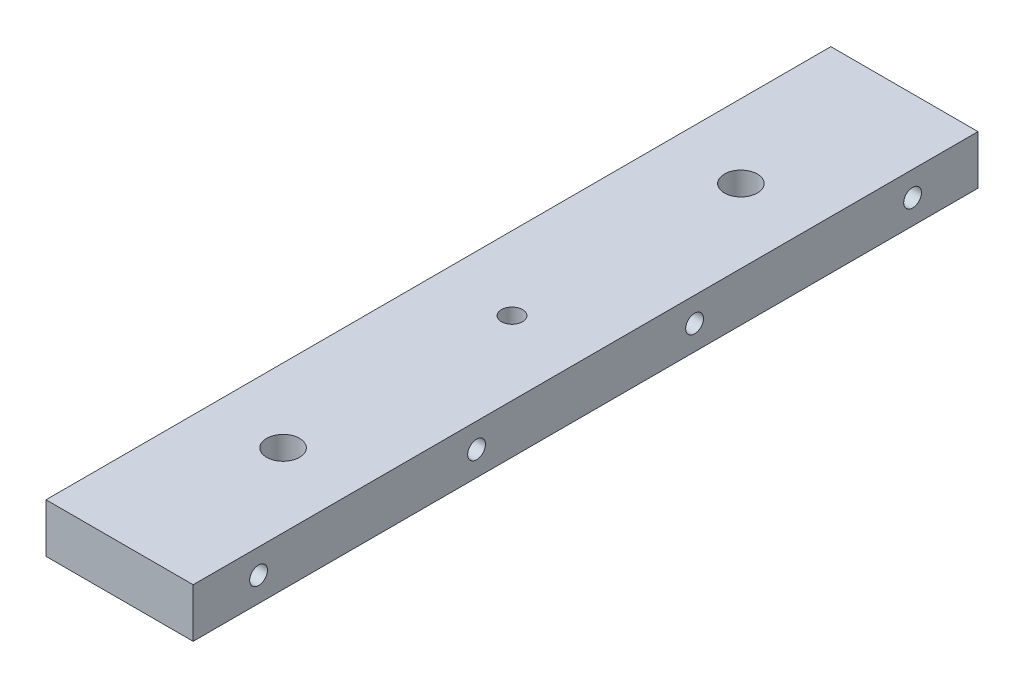
SolidWorks part; units mm, degrees
ref_plane "Front Plane" through (0, 0, 0) normal (0, 0, 1) x (1, 0, 0)
ref_plane "Top Plane" through (0, 0, 0) normal (0, 1, 0) x (1, 0, 0)
ref_plane "Right Plane" through (0, 0, 0) normal (1, 0, 0) x (0, 0, -1)
sketch "Sketch2" plane through (0, 0, 0) normal (0, 1, 0) x (1, 0, 0)
  line L0 (0, 0) -> (0, 152.4)
  line L1 (0, 152.4) -> (28.575, 152.4)
  line L2 (28.575, 152.4) -> (28.575, 0)
  line L3 (28.575, 0) -> (0, 0)
  dimension "D1" = 152.4
  dimension "D2" = 28.575
extrude "Boss-Extrude1" add sketch "Sketch2" along normal blind 9.525
sketch "Sketch3" plane through (0, 0, 0) normal (-1, 0, 0) x (0, 0, 1)
  line L3 (-152.4, 9.525) -> (0, 9.525) construction
  line L4 (-152.4, 9.525) -> (-152.4, 0) construction
  point P6 (-139.7, 4.7625)
  point P14 (-139.7, 4.7625)
  dimension "D1" = 4.7625
  dimension "D2" = 12.7
sketch "Sketch8" plane through (0, 0, 0) normal (-1, 0, 0) x (0, 0, 1)
  point P0 (-139.7, 4.7625)
hole_wizard "#5 Clearance Hole3" positions "Sketch8" profile "Sketch9" hole size "#5" standard "ANSI Inch"
sketch "Sketch9" plane through (0, 4.7625, -139.7) normal (0, 1, 0) x (0, 0, 1)
  line L0 (0, 0) -> (0, 13.7378)
  line L1 (0, 13.7378) -> (1.7272, 12.7)
  line L2 (1.7272, 12.7) -> (1.7272, 0)
  line L5 (1.7272, 0) -> (0, 0)
  line L10 (0, 13.7378) -> (-1.7272, 12.7) construction
  line L11 (0, -6.35) -> (0, 107.95) construction
  dimension "Hole Dia." = 3.4544
  dimension "Hole Depth" = 12.7
  dimension "Drill Angle" = 118
pattern_linear "LPattern1" count 4 spacing 42.3333 along (0, 0, 1) of "#5 Clearance Hole3"
sketch "Sketch10" plane through (28.575, 0, 0) normal (1, 0, 0) x (0, 0, -1)
  line L0 (0, 9.525) -> (0, 0) construction
  line L1 (0, 9.525) -> (152.4, 9.525) construction
  point P0 (12.7, 4.7625)
  point P1 (12.7, 4.7625)
  point P5 (0, 4.7625)
  point P9 (12.7, 4.7625)
  dimension "D1" = 12.7
  dimension "D2" = 4.7625
hole_wizard "#5 Clearance Hole4" positions "Sketch10" profile "Sketch11" hole size "#5" standard "ANSI Inch"
sketch "Sketch11" plane through (28.575, 4.7625, -12.7) normal (0, 1, 0) x (0, 0, -1)
  line L0 (0, 0) -> (0, 13.7378)
  line L1 (0, 13.7378) -> (1.7272, 12.7)
  line L2 (1.7272, 12.7) -> (1.7272, 0)
  line L5 (1.7272, 0) -> (0, 0)
  line L10 (0, 13.7378) -> (-1.7272, 12.7) construction
  line L11 (0, -6.35) -> (0, 107.95) construction
  dimension "Hole Dia." = 3.4544
  dimension "Hole Depth" = 12.7
  dimension "Drill Angle" = 118
pattern_linear "LPattern2" count 4 spacing 42.3333 along (0, 0, -1) of "#5 Clearance Hole4"
sketch "Sketch12" plane through (0, 9.525, 0) normal (0, 1, 0) x (1, 0, 0)
  line L0 (28.575, 0) -> (28.575, 152.4) construction
  line L2 (0, 0) -> (28.575, 0) construction
  circle A0 centre (14.2875, 76.2) radius 2.05
  circle A1 centre (14.2875, 31.75) radius 3.2004
  circle A2 centre (14.2875, 120.65) radius 3.2004
  point P0 (14.2875, 120.65)
  point P1 (14.2875, 76.2)
  point P2 (14.2875, 31.75)
  dimension "D7" = 4.1
  dimension "D8" = 6.4008
  dimension "D9" = 6.4008
  dimension "D1" = 14.2875
  dimension "D2" = 14.2875
  dimension "D3" = 14.2875
  dimension "D4" = 76.2
  dimension "D5" = 44.45
  dimension "D6" = 44.45
extrude "Cut-Extrude1" cut sketch "Sketch12" against normal through all
